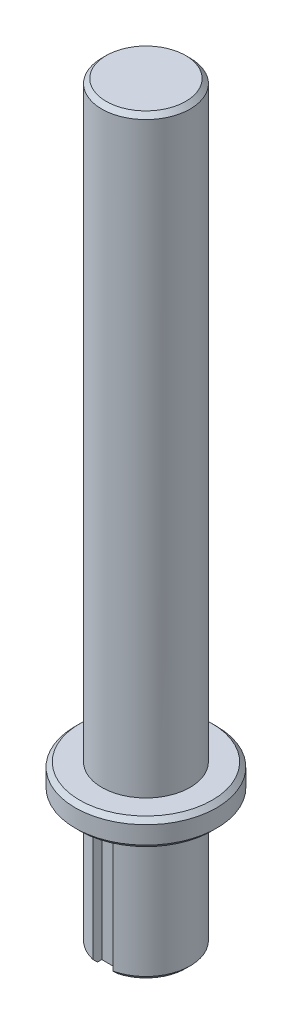
SolidWorks part; units mm, degrees
ref_plane "Front Plane" through (0, 0, 0) normal (0, 0, 1) x (1, 0, 0)
ref_plane "Top Plane" through (0, 0, 0) normal (0, 1, 0) x (1, 0, 0)
ref_plane "Right Plane" through (0, 0, 0) normal (1, 0, 0) x (0, 0, -1)
sketch "Sketch1" plane through (0, 0, 0) normal (0, 0, 1) x (1, 0, 0)
  line L0 (0, 0) -> (5, 0)
  line L3 (5, 18) -> (5, 85)
  line L4 (5, 85) -> (0, 85)
  line L5 (0, 85) -> (0, 0)
  line L6 (5, 18) -> (8, 18)
  line L7 (8, 18) -> (8, 15)
  line L8 (8, 15) -> (5, 15)
  line L9 (5, 15) -> (5, 0)
  dimension "D1" = 5
  dimension "D2" = 5
  dimension "D3" = 3
  dimension "D4" = 8
  dimension "D5" = 15
  dimension "D6" = 85
revolve "Revolve1" add sketch "Sketch1" angle 360 about L5
sketch "Sketch2" plane through (0, 0, 0) normal (0, -1, 0) x (1, 0, 0)
  line L1 (-1.125, 6.125) -> (1.125, 6.125)
  line L2 (-1.125, 6.125) -> (-1.125, 3.875)
  line L3 (-1.125, 3.875) -> (1.125, 3.875)
  line L4 (1.125, 6.125) -> (1.125, 3.875)
  line L5 (-1.125, 6.125) -> (1.125, 3.875) construction
  line L6 (-1.125, 3.875) -> (1.125, 6.125) construction
  circle A0 centre (0, 0) radius 5 construction
  point P0 (0, 5)
  dimension "D1" = 2.25
extrude "Cut-Extrude1" cut sketch "Sketch2" against normal up to surface (15 mm away) up to face at (-8, 15, 0)
chamfer "Chamfer1" distance 0.5 angle 45 2 edges at (-8, 15, 0) (-8, 18, 0)
chamfer "Chamfer2" distance 0.5 angle 45 2 edges at (-5, 85, 0) (0, 0, -5)
ref_axis "Axis1" through (0, 18, 0) along (0, 1, 0)
